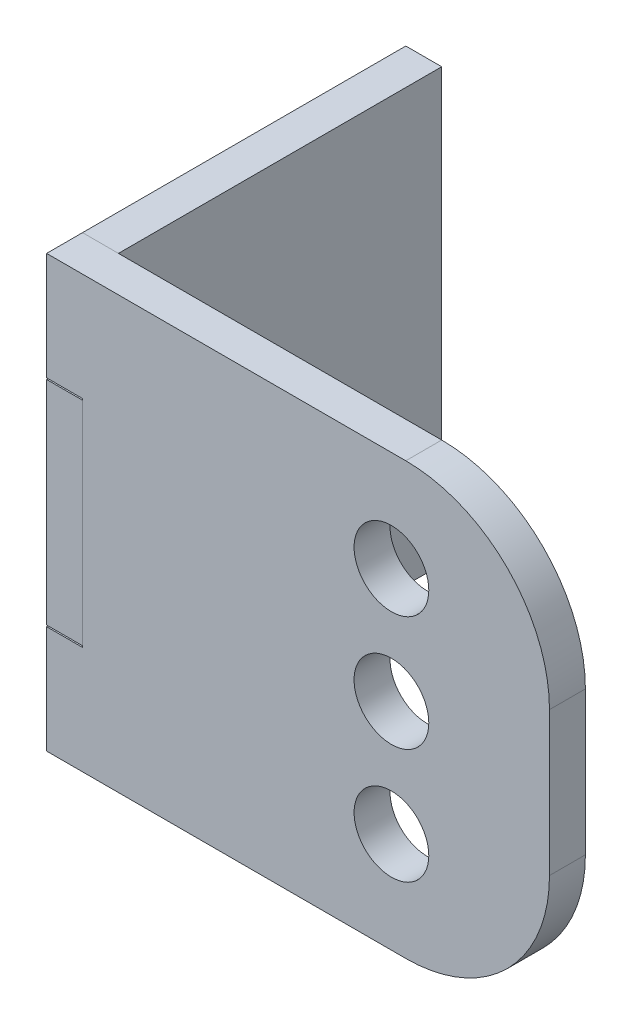
SolidWorks part; units mm, degrees
material "AISI 4130 Steel, annealed at 865C"
ref_plane "Front Plane" through (0, 0, 0) normal (0, 0, 1) x (1, 0, 0)
ref_plane "Top Plane" through (0, 0, 0) normal (0, 1, 0) x (1, 0, 0)
ref_plane "Right Plane" through (0, 0, 0) normal (1, 0, 0) x (0, 0, -1)
sketch "Sketch1" plane through (0, 0, 0) normal (0, 0, 1) x (1, 0, 0)
  line L0 (0, -374.8954) -> (0, 18369.8741) construction
  line L1 (0, 9.525) -> (3.175, 9.525)
  line L6 (0, 19.05) -> (44.45, 19.05)
  line L7 (0, 19.05) -> (0, -19.05)
  line L8 (0, -19.05) -> (44.45, -19.05)
  line L9 (44.45, 19.05) -> (44.45, -19.05)
  line L10 (22.225, -19.05) -> (22.225, 19.05) construction
  line L11 (0, 0) -> (44.45, 0) construction
  line L12 (3.175, 9.525) -> (3.175, -9.525)
  line L13 (3.175, -9.525) -> (0, -9.525)
  point P291 (22.225, 0)
  dimension "D1" = 44.45
  dimension "D2" = 38.1
  dimension "D3" = 9.525
  dimension "D4" = 9.525
  dimension "D5" = 3.175
extrude "Boss-Extrude1" add sketch "Sketch1" along normal blind 3.175 contours L12 L13 L7 L8 L9 L6 L1 region at (22.9894, 0, 0)
sketch "Sketch2" plane through (0, 0, 3.175) normal (0, 0, 1) x (1, 0, 0)
  line L0 (30.48, 10.16) -> (30.48, -10.16) construction
  line L1 (0, 0) -> (44.45, 0) construction
  line L4 (44.45, 19.05) -> (44.45, -19.05) construction
  circle A0 centre (30.48, 10.16) radius 3.302
  circle A1 centre (30.48, -10.16) radius 3.302
  circle A2 centre (30.48, 0) radius 3.302
  point P4 (30.48, 0)
  dimension "D1" = 6.604
  dimension "D2" = 30.48
  dimension "D3" = 10.16
extrude "Cut-Extrude1" cut sketch "Sketch2" against normal through all both and the other way through all
sketch "Sketch3" plane through (0, 0, 0) normal (0, 0, -1) x (-1, 0, 0)
  line L1 (0, 19.05) -> (-3.175, 19.05)
  line L2 (0, 19.05) -> (0, -19.05)
  line L3 (0, -19.05) -> (-3.175, -19.05)
  line L4 (-3.175, 19.05) -> (-3.175, -19.05)
  line L5 (-1.5875, -19.05) -> (-1.5875, 19.05) construction
  line L6 (0, 0) -> (-3.175, 0) construction
  line L7 (-3.175, 9.525) -> (0, 9.525)
  line L8 (0, 9.525) -> (-3.175, 9.525) construction
  line L9 (-3.175, -9.525) -> (0, -9.525)
  line L10 (-3.175, -9.525) -> (0, -9.525) construction
  line L11 (0, -19.05) -> (-44.45, -19.05) construction
  line L12 (-3.175, 9.398) -> (0, 9.398)
  line L13 (-3.175, -9.398) -> (0, -9.398)
  point P148 (-1.5875, 0)
  line M26 (-3.175, -9.525) -> (-3.175, 9.525)
  line M33 (0, -9.525) -> (-3.175, -9.525)
  dimension "D1" = 3.175
  dimension "D2" = 0.127
  dimension "D3" = 0.127
extrude "Boss-Extrude2" add sketch "Sketch3" along normal blind 28.575 contours L4 L7 L2 L1 | L9 L4 L3 L2 | L4 L9 L2 L7 | L4 L13 L2 L12 | L13 L2 M26 M33 region at (1.5875, 14.2875, 0) region at (1.5875, 9.4615, 0) region at (1.5875, 0, 0) region at (1.5875, -9.4615, 0) region at (1.5875, -14.2875, 0)
extrude "Boss-Extrude5" add sketch "Sketch3<4>" against normal blind 3.175 contours L4 L13 L2 L12 region at (1.5875, 0, 0)
sketch "Sketch3<4>" plane through (0, 0, 0) normal (0, 0, -1) x (-1, 0, 0) same geometry as "Sketch3"
fillet "Fillet1" radius 12.7 2 edges at (44.45, -19.05, 1.5875) (44.45, 19.05, 1.5875)
